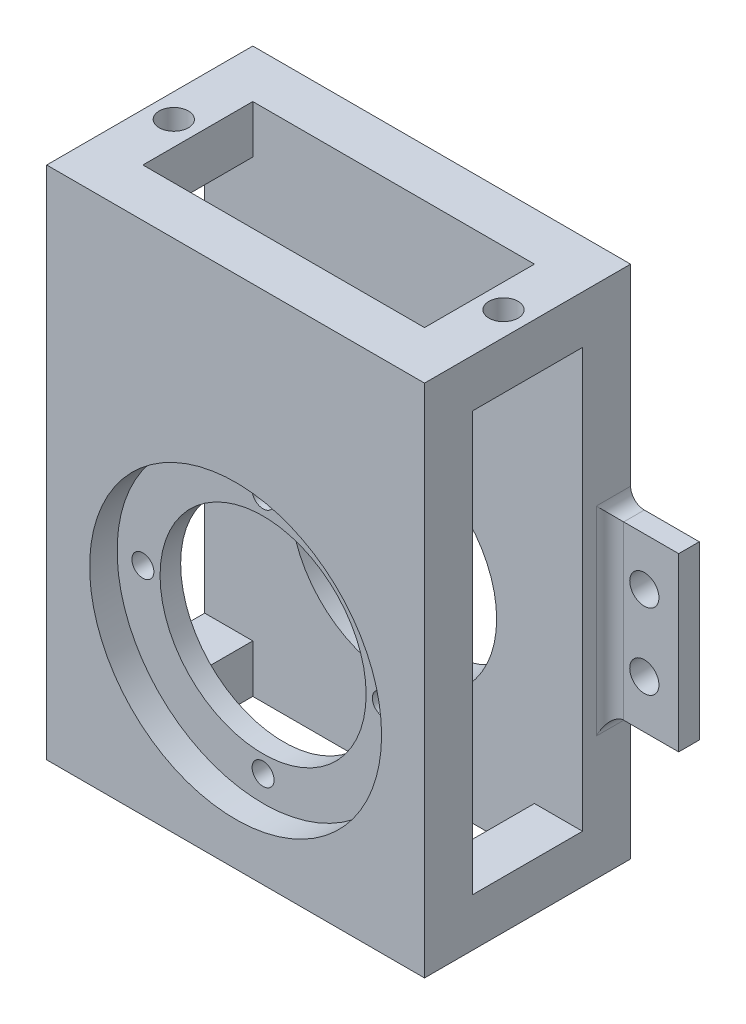
SolidWorks part; units mm, degrees
ref_plane "Front Plane" through (0, 0, 0) normal (0, 0, 1) x (1, 0, 0)
ref_plane "Top Plane" through (0, 0, 0) normal (0, 1, 0) x (1, 0, 0)
ref_plane "Right Plane" through (0, 0, 0) normal (1, 0, 0) x (0, 0, -1)
sketch "Sketch1" plane through (0, 0, 0) normal (0, 0, 1) x (1, 0, 0)
  line L1 (-27.5, 47.5) -> (27.5, 47.5)
  line L2 (-27.5, 47.5) -> (-27.5, -27.5)
  line L3 (-27.5, -27.5) -> (27.5, -27.5)
  line L4 (27.5, 47.5) -> (27.5, -27.5)
  dimension "D1" = 55
  dimension "D2" = 75
  dimension "D3" = 27.5
  dimension "D4" = 27.5
extrude "Boss-Extrude1" add sketch "Sketch1" along normal blind 30
sketch "Sketch4" plane through (0, 47.5, 0) normal (0, 1, 0) x (1, 0, 0)
  line L0 (-27.5, -30) -> (-27.5, 0) construction
  line L1 (-20.5, -7) -> (20.5, -7)
  line L2 (-20.5, -7) -> (-20.5, -23)
  line L3 (-20.5, -23) -> (20.5, -23)
  line L4 (20.5, -7) -> (20.5, -23)
  line L5 (27.5, 0) -> (-27.5, 0) construction
  dimension "D1" = 41
  dimension "D2" = 7
  dimension "D3" = 16
  dimension "7" = 7
extrude "Cut-Extrude1" cut sketch "Sketch4" against normal through all
sketch "Sketch5" plane through (27.5, 0, 0) normal (1, 0, 0) x (0, 0, -1)
  line L0 (-30, 47.5) -> (0, 47.5) construction
  line L1 (-23, 40.5) -> (-7, 40.5)
  line L2 (-23, 40.5) -> (-23, -20.5)
  line L3 (-23, -20.5) -> (-7, -20.5)
  line L4 (-7, 40.5) -> (-7, -20.5)
  line L5 (0, -27.5) -> (0, 47.5) construction
  line L6 (-30, -27.5) -> (0, -27.5) construction
  dimension "D1" = 7
  dimension "D2" = 7
  dimension "D3" = 16
  dimension "D4" = 7
extrude "Cut-Extrude2" cut sketch "Sketch5" against normal blind 60
sketch "Sketch7" plane through (0, 0, 30) normal (0, 0, 1) x (1, 0, 0)
  circle A0 centre (0, 0) radius 21.25
  dimension "D1" = 42.5
extrude "Cut-Extrude3" cut sketch "Sketch7" against normal blind 4
sketch "Sketch8" plane through (0, 0, 26) normal (0, 0, 1) x (1, 0, 0)
  circle A0 centre (0, 0) radius 15
  dimension "D1" = 30
extrude "Cut-Extrude4" cut sketch "Sketch8" against normal blind 50
sketch "Sketch9" plane through (0, 0, 26) normal (0, 0, 1) x (1, 0, 0)
  circle A0 centre (0, 17.5) radius 1.6
  circle A1 centre (17.5, 0) radius 1.6
  circle A2 centre (0, -17.5) radius 1.6
  circle A3 centre (-17.5, 0) radius 1.6
  point P12 (0, 0)
  dimension "D1" = 3.2
  dimension "D2" = 17.5
  dimension "D3" = 4
extrude "Cut-Extrude5" cut sketch "Sketch9" against normal blind 10
sketch "Sketch11" plane through (0, 47.5, 0) normal (0, 1, 0) x (1, 0, 0)
  line L1 (-27.5, -30) -> (-27.5, 0) construction
  line L2 (27.5, -30) -> (27.5, 0) construction
  line L3 (20.5, -7) -> (-20.5, -7) construction
  circle A0 centre (-24, -15) radius 2.125
  circle A1 centre (24, -15) radius 2.125
  dimension "D1" = 4.25
  dimension "D2" = 4.25
  dimension "D3" = 3.5
  dimension "D4" = 3.5
  dimension "D5" = 8
extrude "Cut-Extrude6" cut sketch "Sketch11" against normal blind 10
sketch "Sketch15" plane through (0, 0, 0) normal (0, 0, -1) x (-1, 0, 0)
  line L0 (-27.5, -27.5) -> (-27.5, 47.5) construction
  line L1 (-27.5, 17.5) -> (-37.5, 17.5)
  line L2 (-27.5, 17.5) -> (-27.5, -7.5)
  line L3 (-27.5, -7.5) -> (-37.5, -7.5)
  line L4 (-37.5, 17.5) -> (-37.5, -7.5)
  line L5 (0, 12.2574) -> (0, -13.2812) construction
  line L6 (27.5, -27.5) -> (-27.5, -27.5) construction
  line L7 (37.5, 17.5) -> (37.5, -7.5)
  line L8 (27.5, -7.5) -> (37.5, -7.5)
  line L9 (27.5, 17.5) -> (27.5, -7.5)
  line L10 (27.5, 17.5) -> (37.5, 17.5)
  dimension "D1" = 25
  dimension "D2" = 20
  dimension "D3" = 10
extrude "Boss-Extrude3" add sketch "Sketch15" against normal blind 3
sketch "Sketch16" plane through (0, 0, 0) normal (0, 0, -1) x (-1, 0, 0)
  line L0 (0, 11.1792) -> (0, -9.5077) construction
  line L1 (-37.5, 17.5) -> (-37.5, -7.5) construction
  line L2 (-37.5, -7.5) -> (-27.5, -7.5) construction
  line L3 (-27.5, 17.5) -> (-37.5, 17.5) construction
  circle A0 centre (-32.5, 10.5) radius 2.125
  circle A1 centre (-32.5, -0.5) radius 2.125
  circle A2 centre (32.5, -0.5) radius 2.125
  circle A3 centre (32.5, 10.5) radius 2.125
  dimension "D1" = 4.25
  dimension "D2" = 4.25
  dimension "D3" = 5
  dimension "D4" = 5
  dimension "D5" = 7
  dimension "D6" = 7
extrude "Cut-Extrude8" cut sketch "Sketch16" against normal blind 3
fillet "Fillet2" radius 2 6 edges at (27.5, -7.5, 1.5) (27.5, 5, 3) (27.5, 17.5, 1.5) (-27.5, -7.5, 1.5) (-27.5, 5, 3) (-27.5, 17.5, 1.5)
